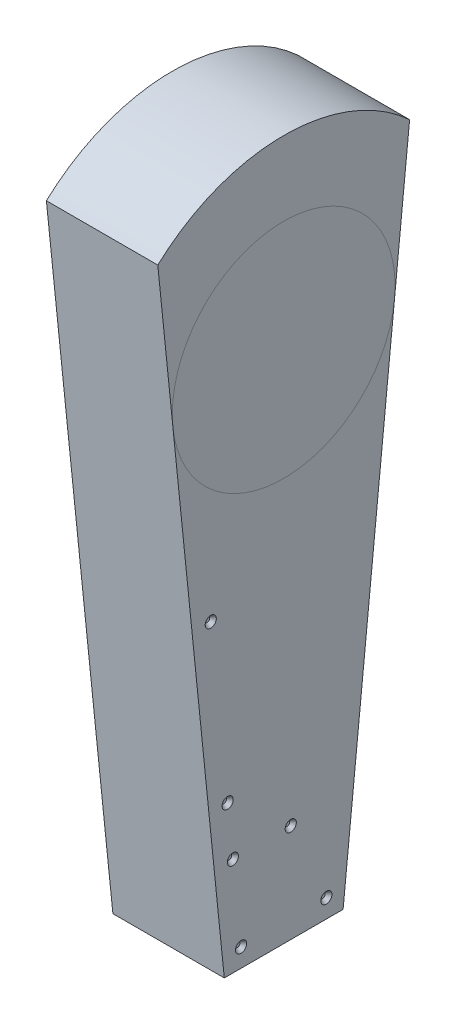
SolidWorks part; units mm, degrees
ref_plane "Alzado" through (0, 0, 0) normal (0, 0, 1) x (1, 0, 0)
ref_plane "Planta" through (0, 0, 0) normal (0, 1, 0) x (1, 0, 0)
ref_plane "Vista lateral" through (0, 0, 0) normal (1, 0, 0) x (0, 0, -1)
sketch "Croquis1" plane through (0, 0, 0) normal (1, 0, 0) x (0, 0, -1)
  line L0 (-40.64, -351.79) -> (-86.1359, 93.3253)
  line L1 (0, 0) -> (0, -351.79) construction
  line L2 (40.64, -351.79) -> (86.1359, 93.3253)
  line L7 (-40.64, -351.79) -> (40.64, -351.79)
  circle A0 centre (0, 0) radius 127 construction
  circle A1 centre (0, 0) radius 76.2 construction
  arc A4 (86.1359, 93.3253) -> (-86.1359, 93.3253) centre (0, 0) ccw
  dimension "D1" = 254
  dimension "D2" = 152.4
  dimension "D3" = 351.79
extrude "Saliente-Extruir1" add sketch "Croquis1" along normal blind 76.2
sketch "Croquis2" plane through (76.2, 0, 0) normal (1, 0, 0) x (0, 0, -1)
  circle A0 centre (0, 0) radius 76.2
split line "Línea de partición1"
sketch "Croquis3" plane through (0, -351.79, 0) normal (0, -1, 0) x (1, 0, 0)
  line L0 (0, 0) -> (38.1, 0) construction
  line L1 (38.1, 0) -> (38.1, 40.64) construction
  line L2 (76.2, 40.64) -> (0, 40.64) construction
  circle A0 centre (38.1, 0) radius 25.4
  dimension "D1" = 50.8
split line "Línea de partición2"
sketch "Croquis4" plane through (76.2, 0, 0) normal (1, 0, 0) x (0, 0, -1)
  line L6 (-53.5213, -100.8643) -> (-29.1719, -339.09) construction
  line L7 (-29.1719, -339.09) -> (29.1719, -339.09) construction
  line L8 (29.1719, -339.09) -> (53.2304, -103.711) construction
  circle A0 centre (-49.9171, -136.1268) radius 3.81
  circle A1 centre (-38.3624, -249.174) radius 3.81
  circle A2 centre (-34.7681, -284.3391) radius 3.81
  circle A3 centre (-29.1719, -339.09) radius 3.81
  circle A4 centre (29.1719, -339.09) radius 3.81
  circle A5 centre (4.8195, -284.3391) radius 3.81
  dimension "D1" = 7.62
extrude "Cortar-Extruir1" cut sketch "Croquis4" against normal blind 2.54 draft 39
sketch "Croquis5" plane through (0, 0, 0) normal (-1, 0, 0) x (0, 0, 1)
  line L3 (0, -339.09) -> (0, -280.0103) construction
  line L6 (-29.1719, -339.09) -> (-72.8345, 88.0887) construction
  line L7 (72.8345, 88.0887) -> (29.1719, -339.09) construction
  line L8 (29.1719, -339.09) -> (-29.1719, -339.09) construction
  circle A1 centre (-12.5569, -339.09) radius 3.81
  arc A2 (72.8345, 88.0887) -> (-72.8345, 88.0887) centre (0, 0) ccw construction
  circle A3 centre (12.5569, -339.09) radius 3.81
  circle A4 centre (-34.1821, -290.0722) radius 3.81
  circle A5 centre (-48.2655, -152.2857) radius 3.81
  circle A6 centre (-69.7519, 57.9299) radius 3.81
  circle A7 centre (-48.2655, 103.6095) radius 3.81
  circle A8 centre (48.2655, 103.6095) radius 3.81
  circle A9 centre (69.7519, 57.9299) radius 3.81
  circle A10 centre (48.2655, -152.2857) radius 3.81
  dimension "D1" = 7.62
extrude "Cortar-Extruir2" cut sketch "Croquis5" against normal blind 2.54 draft 39
ref_point "Point1"
ref_axis "Axis1" through (76.2, 0, 0) along (-1, 0, 0)
ref_axis "Axis2" through (76.2, 0, 0) along (0, -1, 0)
